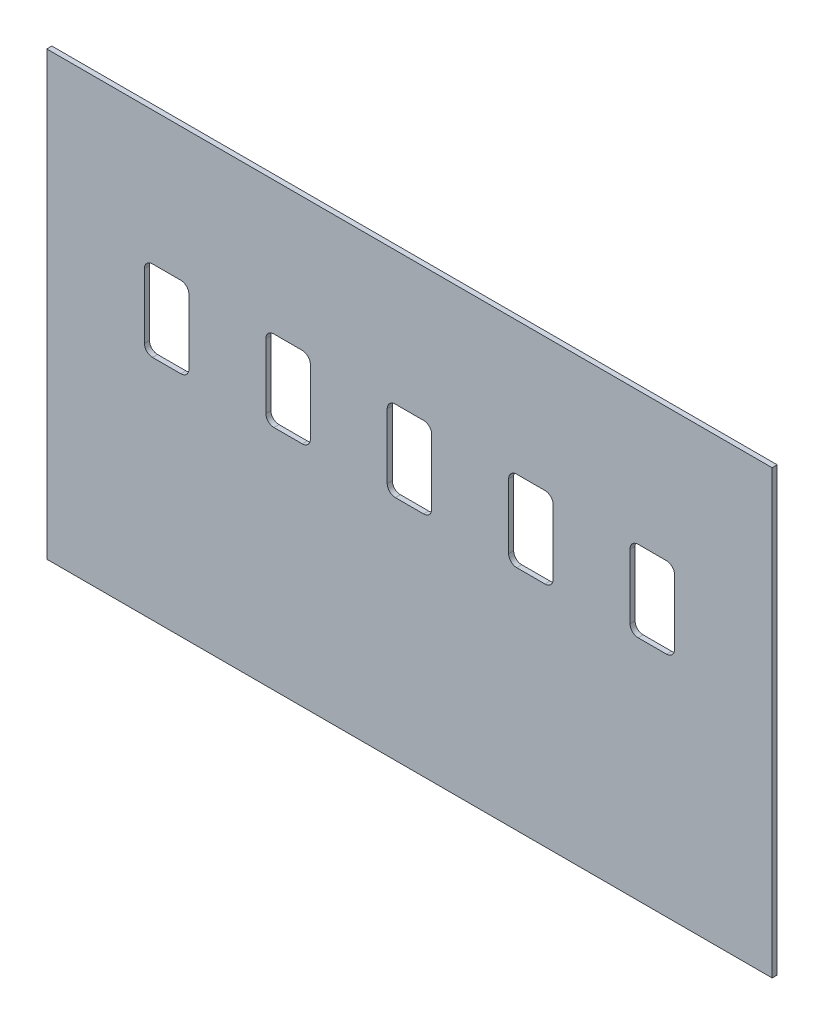
SolidWorks part; units mm, degrees
material "ABS PC"
ref_plane "Front Plane" through (0, 0, 0) normal (0, 0, 1) x (1, 0, 0)
ref_plane "Top Plane" through (0, 0, 0) normal (0, 1, 0) x (1, 0, 0)
ref_plane "Right Plane" through (0, 0, 0) normal (1, 0, 0) x (0, 0, -1)
sketch "Sketch1" plane through (0, 0, 0) normal (0, 0, 1) x (1, 0, 0)
  line L1 (-227.6475, -138.684) -> (227.6475, -138.684)
  line L2 (-227.6475, -138.684) -> (-227.6475, 138.684)
  line L3 (-227.6475, 138.684) -> (227.6475, 138.684)
  line L4 (227.6475, -138.684) -> (227.6475, 138.684)
  line L5 (0, 138.684) -> (0, -138.684) construction
  line L6 (-227.6475, 0) -> (227.6475, 0) construction
  point P0 (0, 0)
  point P4 (-159.0675, 0)
  point P5 (159.0675, 0)
  point P6 (0, 97.0788)
  point P7 (0, -97.0788)
  dimension "Width" = 277.368
  dimension "Break" = 68.58
  dimension "D2" = 68.58
  dimension "D1" = 41.6052
  dimension "D3" = 41.6052
  dimension "D4" = 455.295
sketch "Sketch2" plane through (0, 0, 0) normal (1, 0, 0) x (0, 0, -1)
  line L0 (-1.5875, -138.684) -> (1.5875, -138.684)
  dimension "Thickness" = 3.175
sketch "Sketch3" plane through (0, 0, 0) normal (0, 0, 1) x (1, 0, 0)
  line L0 (-227.6475, -138.684) -> (-227.6475, 138.684) construction
  line L1 (-227.6475, -138.684) -> (227.6475, -138.684) construction
  line L2 (227.6475, -138.684) -> (227.6475, 138.684) construction
  line L3 (-227.6475, 138.684) -> (227.6475, 138.684) construction
  line L4 (-227.6475, -138.684) -> (-227.6475, 138.684)
  line L5 (-227.6475, -138.684) -> (227.6475, -138.684)
  line L6 (227.6475, -138.684) -> (227.6475, 138.684)
  line L7 (-227.6475, 138.684) -> (227.6475, 138.684)
extrude "Boss-Extrude1" add sketch "Sketch3" along normal mid plane 3.175
sketch "Sketch4" plane through (0, 0, 1.5875) normal (0, 0, 1) x (1, 0, 0)
  line L0 (-227.6475, 29.591) -> (-158.75, 29.591) construction
  line L1 (-82.55, 29.591) -> (-82.55, 54.991) construction
  line L2 (-82.55, 54.991) -> (-90.17, 54.991) construction
  line L3 (-158.75, 29.591) -> (-158.75, 54.991) construction
  line L8 (-158.75, 29.591) -> (-82.55, 29.591) construction
  line L9 (-82.55, 29.591) -> (-6.35, 29.591) construction
  line L10 (-6.35, 29.591) -> (69.85, 29.591) construction
  line L11 (69.85, 29.591) -> (146.05, 29.591) construction
  line L12 (-82.55, 29.591) -> (-82.55, 4.191) construction
  line L13 (-82.55, 4.191) -> (-62.23, 4.191) construction
  line L16 (-158.75, 54.991) -> (-166.37, 54.991) construction
  line L17 (-158.75, 29.591) -> (-158.75, 4.191) construction
  line L18 (-158.75, 4.191) -> (-138.43, 4.191) construction
  line L19 (-6.35, 29.591) -> (-6.35, 54.991) construction
  line L20 (-161.29, 54.991) -> (-143.51, 54.991)
  line L21 (-166.37, 49.911) -> (-166.37, 9.271)
  line L22 (-161.29, 4.191) -> (-143.51, 4.191)
  line L23 (-138.43, 49.911) -> (-138.43, 9.271)
  line L24 (-6.35, 54.991) -> (-13.97, 54.991) construction
  line L25 (-6.35, 29.591) -> (-6.35, 4.191) construction
  line L26 (-6.35, 4.191) -> (13.97, 4.191) construction
  line L27 (69.85, 29.591) -> (69.85, 54.991) construction
  line L28 (-8.89, 54.991) -> (8.89, 54.991)
  line L29 (-13.97, 49.911) -> (-13.97, 9.271)
  line L30 (-8.89, 4.191) -> (8.89, 4.191)
  line L31 (13.97, 49.911) -> (13.97, 9.271)
  line L32 (69.85, 54.991) -> (62.23, 54.991) construction
  line L33 (69.85, 29.591) -> (69.85, 4.191) construction
  line L34 (69.85, 4.191) -> (90.17, 4.191) construction
  line L35 (146.05, 29.591) -> (146.05, 54.991) construction
  line L36 (67.31, 54.991) -> (85.09, 54.991)
  line L37 (62.23, 49.911) -> (62.23, 9.271)
  line L38 (67.31, 4.191) -> (85.09, 4.191)
  line L39 (90.17, 49.911) -> (90.17, 9.271)
  line L40 (146.05, 54.991) -> (138.43, 54.991) construction
  line L41 (146.05, 29.591) -> (146.05, 4.191) construction
  line L42 (146.05, 4.191) -> (166.37, 4.191) construction
  line L44 (143.51, 54.991) -> (161.29, 54.991)
  line L45 (138.43, 49.911) -> (138.43, 9.271)
  line L46 (143.51, 4.191) -> (161.29, 4.191)
  line L47 (166.37, 49.911) -> (166.37, 9.271)
  line L48 (-85.09, 54.991) -> (-67.31, 54.991)
  line L49 (-90.17, 49.911) -> (-90.17, 9.271)
  line L50 (-85.09, 4.191) -> (-67.31, 4.191)
  line L51 (-62.23, 49.911) -> (-62.23, 9.271)
  arc A0 (138.43, 9.271) -> (143.51, 4.191) centre (143.51, 9.271) ccw
  arc A1 (166.37, 9.271) -> (161.29, 4.191) centre (161.29, 9.271) cw
  arc A2 (161.29, 54.991) -> (166.37, 49.911) centre (161.29, 49.911) cw
  arc A3 (138.43, 49.911) -> (143.51, 54.991) centre (143.51, 49.911) cw
  arc A4 (62.23, 9.271) -> (67.31, 4.191) centre (67.31, 9.271) ccw
  arc A5 (90.17, 9.271) -> (85.09, 4.191) centre (85.09, 9.271) cw
  arc A6 (85.09, 54.991) -> (90.17, 49.911) centre (85.09, 49.911) cw
  arc A7 (67.31, 54.991) -> (62.23, 49.911) centre (67.31, 49.911) ccw
  arc A8 (-13.97, 9.271) -> (-8.89, 4.191) centre (-8.89, 9.271) ccw
  arc A9 (13.97, 9.271) -> (8.89, 4.191) centre (8.89, 9.271) cw
  arc A10 (8.89, 54.991) -> (13.97, 49.911) centre (8.89, 49.911) cw
  arc A11 (-8.89, 54.991) -> (-13.97, 49.911) centre (-8.89, 49.911) ccw
  arc A15 (-138.43, 9.271) -> (-143.51, 4.191) centre (-143.51, 9.271) cw
  arc A16 (-143.51, 54.991) -> (-138.43, 49.911) centre (-143.51, 49.911) cw
  arc A17 (-166.37, 49.911) -> (-161.29, 54.991) centre (-161.29, 49.911) cw
  arc A18 (-166.37, 9.271) -> (-161.29, 4.191) centre (-161.29, 9.271) ccw
  arc A19 (-90.17, 9.271) -> (-85.09, 4.191) centre (-85.09, 9.271) ccw
  arc A20 (-62.23, 9.271) -> (-67.31, 4.191) centre (-67.31, 9.271) cw
  arc A21 (-67.31, 54.991) -> (-62.23, 49.911) centre (-67.31, 49.911) cw
  arc A22 (-85.09, 54.991) -> (-90.17, 49.911) centre (-85.09, 49.911) ccw
  point P14 (-152.4, 54.991)
  point P15 (-227.6475, 29.591)
  point P16 (-76.2, 54.991)
  point P17 (-90.17, 29.591)
  point P18 (-13.97, 29.591)
  point P95 (62.23, 29.591)
  point P96 (138.43, 29.591)
  point P97 (0, 54.991)
  point P98 (76.2, 54.991)
  point P99 (152.4, 54.991)
  dimension "D1" = 5.08
  dimension "D2" = 5.08
  dimension "D8" = 27.94
  dimension "D9" = 27.94
  dimension "D10" = 27.94
  dimension "D11" = 27.94
  dimension "D12" = 27.94
  dimension "D3" = 76.2
  dimension "D4" = 76.2
  dimension "D5" = 152.4
  dimension "D6" = 152.4
  dimension "D13" = 25.4
  dimension "D14" = 25.4
extrude "Cut-Extrude1" cut sketch "Sketch4" against normal blind 25.4 contours L21 A18 L22 A15 L23 A16 L20 A17 | A22 L48 A21 L51 A20 L50 A19 L49 | L29 A8 L30 A9 L31 A10 L28 A11 | L37 A4 L38 A5 L39 A6 L36 A7 | A3 L44 A2 L47 A1 L46 A0 L45
equation "\"D1@Boss-Extrude1\" = \"Thickness@Sketch2\""
equation "\"D2@Sketch1\" = \"Break@Sketch1\""
equation "\"D1@Sketch1\"=\"Width@Sketch1\"*0.15"
equation "\"D3@Sketch1\"=\"D1@Sketch1\""
equation "\"SlotWidth\"= 1.1in"
equation "\"D8@Sketch4\"=\"SlotWidth\""
equation "\"D9@Sketch4\"=\"SlotWidth\""
equation "\"D10@Sketch4\"=\"SlotWidth\""
equation "\"D11@Sketch4\"=\"SlotWidth\""
equation "\"D12@Sketch4\"=\"SlotWidth\""
